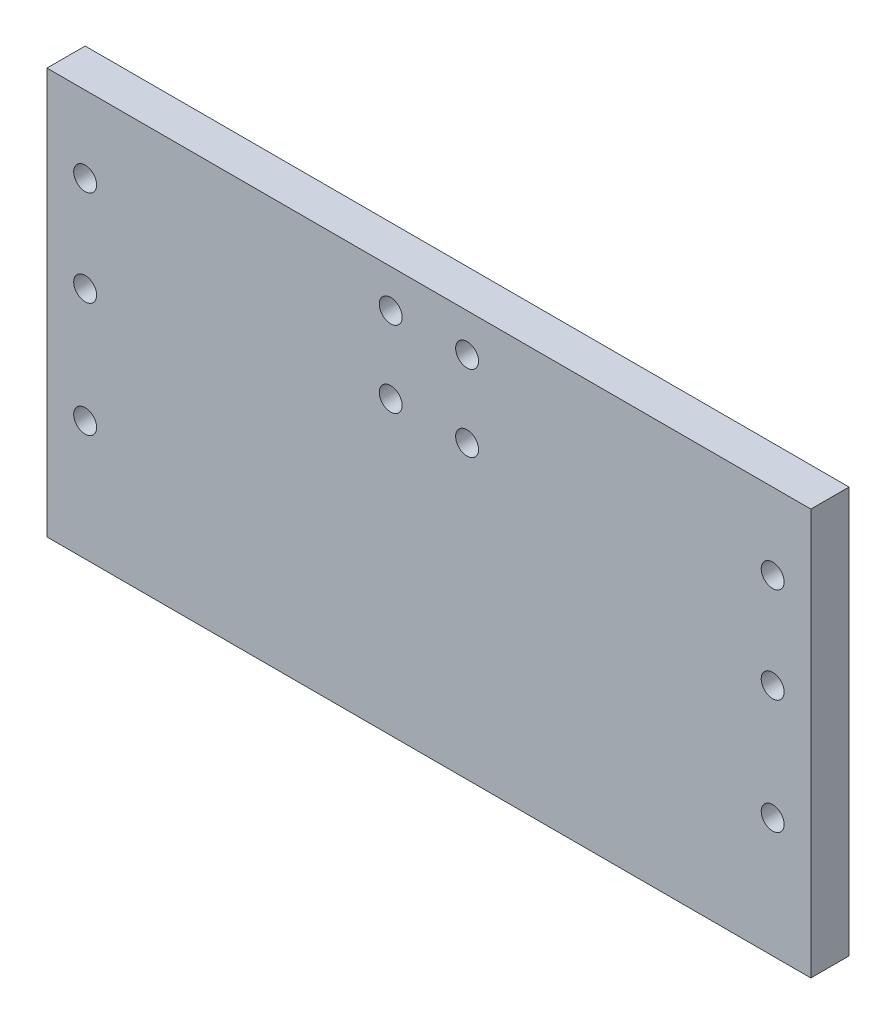
SolidWorks part; units mm, degrees
ref_plane "Front Plane" through (0, 0, 0) normal (0, 0, 1) x (1, 0, 0)
ref_plane "Top Plane" through (0, 0, 0) normal (0, 1, 0) x (1, 0, 0)
ref_plane "Right Plane" through (0, 0, 0) normal (1, 0, 0) x (0, 0, -1)
sketch "Sketch1" plane through (0, 0, 0) normal (0, 0, 1) x (1, 0, 0)
  line L1 (-50, -26.58) -> (50, -26.58)
  line L2 (-50, -26.58) -> (-50, 26.58)
  line L3 (-50, 26.58) -> (50, 26.58)
  line L4 (50, -26.58) -> (50, 26.58)
  line L5 (-50, -26.58) -> (50, 26.58) construction
  line L6 (-50, 26.58) -> (50, -26.58) construction
  point P0 (0, 0)
  dimension "D1" = 100
  dimension "D2" = 53.16
extrude "Boss-Extrude1" add sketch "Sketch1" along normal blind 5
sketch "Sketch2" plane through (0, 0, 5) normal (0, 0, 1) x (1, 0, 0)
  line L0 (50, 26.58) -> (-50, 26.58) construction
  line L1 (-50, 26.58) -> (-50, -26.58) construction
  line L3 (0, -2.75) -> (0, 2.75) construction
  circle A0 centre (-45, 16.58) radius 1.5
  circle A1 centre (-45, 4.08) radius 1.5
  circle A2 centre (-45, -10.92) radius 1.5
  circle A6 centre (45, -10.92) radius 1.5
  circle A7 centre (45, 4.08) radius 1.5
  circle A8 centre (45, 16.58) radius 1.5
  circle A9 centre (-5, 11.58) radius 1.5
  circle A10 centre (-5, 21.58) radius 1.5
  circle A11 centre (5, 11.58) radius 1.5
  circle A12 centre (5, 21.58) radius 1.5
  point P18 (-5, 11.58)
  dimension "D3" = 3
  dimension "D4" = 3
  dimension "D5" = 3
  dimension "D7" = 37.5
  dimension "D8" = 3
  dimension "D9" = 5
  dimension "D11" = 3
  dimension "D1" = 10
  dimension "D2" = 12.5
  dimension "D6" = 5
  dimension "D10" = 10
  dimension "D12" = 5
extrude "Cut-Extrude1" cut sketch "Sketch2" against normal through all
